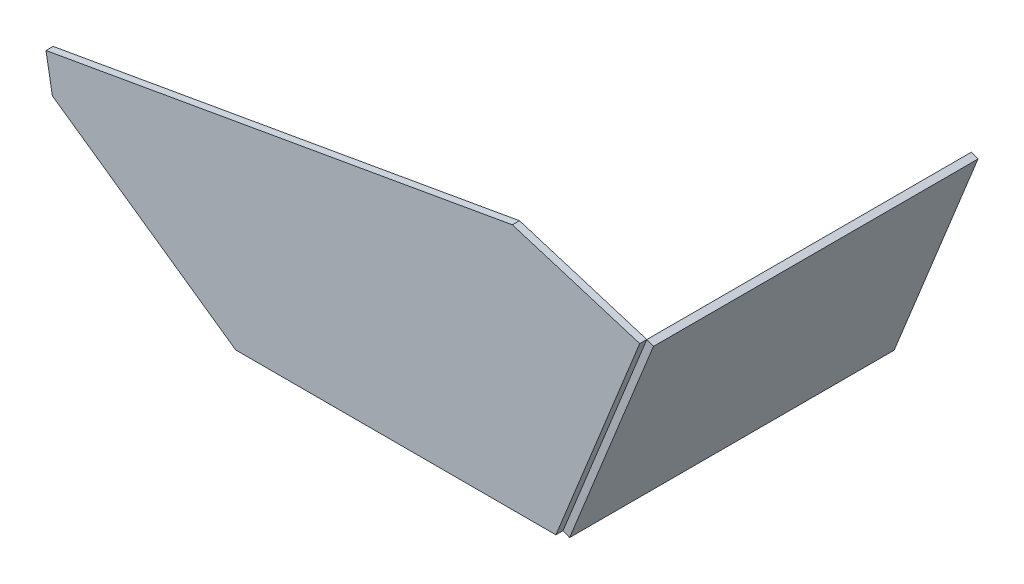
SolidWorks part; units mm, degrees
material "Melamine"
ref_plane "Front Plane" through (0, 0, 0) normal (0, 0, 1) x (1, 0, 0)
ref_plane "Top Plane" through (0, 0, 0) normal (0, 1, 0) x (1, 0, 0)
ref_plane "Right Plane" through (0, 0, 0) normal (1, 0, 0) x (0, 0, -1)
ref_axis "Axis1" through (0, 0, -14.8175) along (0, 0, 1)
sketch "Sketch1" plane through (0, 0, 0) normal (0, 0, 1) x (1, 0, 0)
  line L0 (-137.5, 0) -> (137.5, 0) construction
  line L1 (-137.5, 0) -> (-301.3304, 114.7153) construction
  line L4 (-148.5709, 0) -> (-304.9726, 109.5137) construction
  line L5 (-304.9726, 109.5137) -> (-301.3304, 114.7153) construction
  line L12 (137.5, 0) -> (212.4213, 185.4368) construction
  line L13 (137.5, 0) -> (143.3876, -2.3788)
  line L14 (143.3876, -2.3788) -> (218.3089, 183.058)
  line L15 (218.3089, 183.058) -> (212.4213, 185.4368)
  line L16 (212.4213, 185.4368) -> (137.5, 0)
  line L17 (-137.5, 0) -> (-148.5709, 0) construction
  point P4 (0, 0)
  dimension "D1" = 35
  dimension "D2" = 275
  dimension "D4" = 200
  dimension "D6" = 6.35
  dimension "D7" = 68
  dimension "D8" = 200
  dimension "D9" = 6.35
extrude "Boss-Extrude1" add sketch "Sketch1" along normal blind 290
sketch "Sketch2" plane through (0, 0, 290) normal (0, 0, 1) x (1, 0, 0)
  line L1 (-318.0934, 146.9969) -> (98.6242, 220.4754)
  line L3 (137.5, 0) -> (-148.5709, 0)
  line L4 (-148.5709, 0) -> (-312.4013, 114.7153) construction
  line L5 (137.5, 0) -> (212.4213, 185.4368)
  line L7 (-312.4013, 114.7153) -> (-318.0934, 146.9969)
  line L8 (-312.4013, 114.7153) -> (-308.7591, 119.9169) construction
  line L9 (212.4213, 185.4368) -> (98.6242, 220.4754)
  line L10 (137.5, 0) -> (98.6242, 220.4754) construction
  line L11 (-312.4013, 114.7153) -> (-148.5709, 0)
  line L13 (-148.5709, 0) -> (-137.5, 0) construction
  line L14 (-312.4013, 114.7153) -> (-148.5709, 0) construction
  line L15 (-308.7591, 119.9169) -> (-137.5, 0) construction
  point P7 (-154.128, 0)
  dimension "D1" = 10
  dimension "D2" = 200
  dimension "D3" = 6.35
  dimension "D4" = 35
  dimension "D5" = 200
  dimension "D6" = 275
extrude "Boss-Extrude2" add sketch "Sketch2" along normal blind 6.35 separate body
ref_plane "Plane1" through (0, 0, 0) normal (0.9848, 0.1736, 0) x (0, 0, 1)
